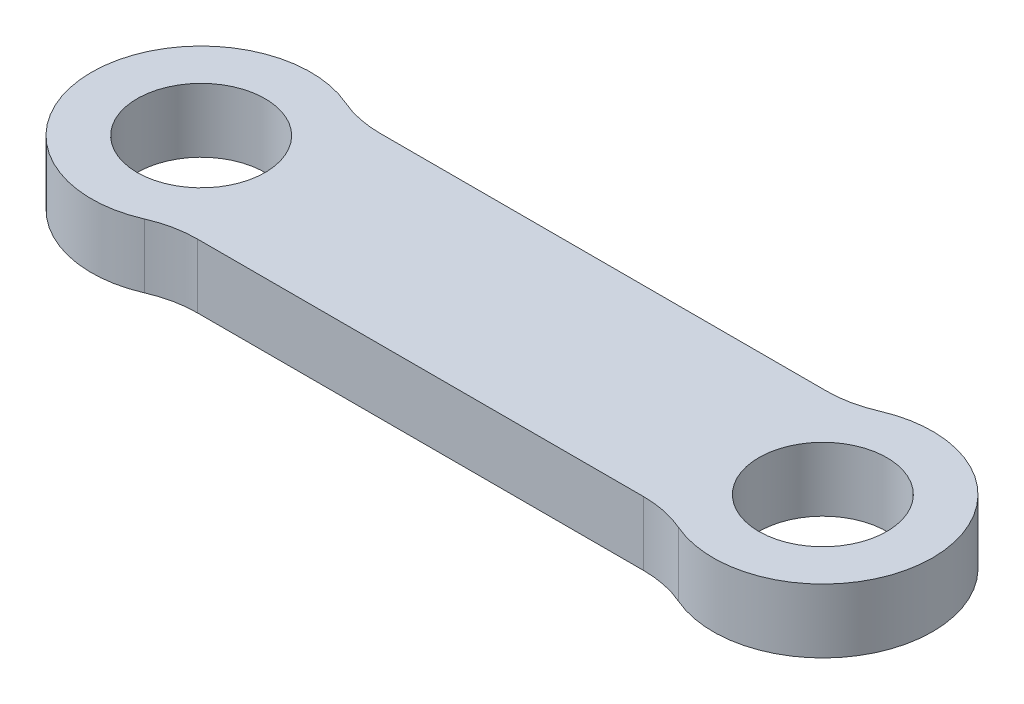
SolidWorks part; units mm, degrees
ref_plane "Front Plane" through (0, 0, 0) normal (0, 0, 1) x (1, 0, 0)
ref_plane "Top Plane" through (0, 0, 0) normal (0, 1, 0) x (1, 0, 0)
ref_plane "Right Plane" through (0, 0, 0) normal (1, 0, 0) x (0, 0, -1)
sketch "Sketch1" plane through (0, 0, 0) normal (0, 1, 0) x (1, 0, 0)
  line L0 (0, 0) -> (17, 0) construction
  line L1 (1.6583, 2.5) -> (15.3417, 2.5)
  line L2 (1.6583, -2.5) -> (15.3417, -2.5)
  circle A0 centre (0, 0) radius 3
  circle A1 centre (17, 0) radius 3
  circle A2 centre (0, 0) radius 1.75
  circle A3 centre (17, 0) radius 1.75
  dimension "D1" = 6
  dimension "D3" = 6
  dimension "D5" = 3.5
  dimension "D6" = 3.5
  dimension "D2" = 17
  dimension "D4" = 2.5
extrude "Boss-Extrude1" add sketch "Sketch1" along normal blind 1.75 contours A2 A0 | L0 A0 L2 A1 | A0 L0 A1 L1 | A1 A3 region at (2.5686, 0, 1.3785) region at (8.5, 0, -1.2943) region at (8.5, 0, 1.2943) region at (14.4314, 0, -1.3785)
fillet "Fillet1" radius 3 4 edges at (1.6583, 0.875, 2.5) (15.3417, 0.875, 2.5) (15.3417, 0.875, -2.5) (1.6583, 0.875, -2.5)
